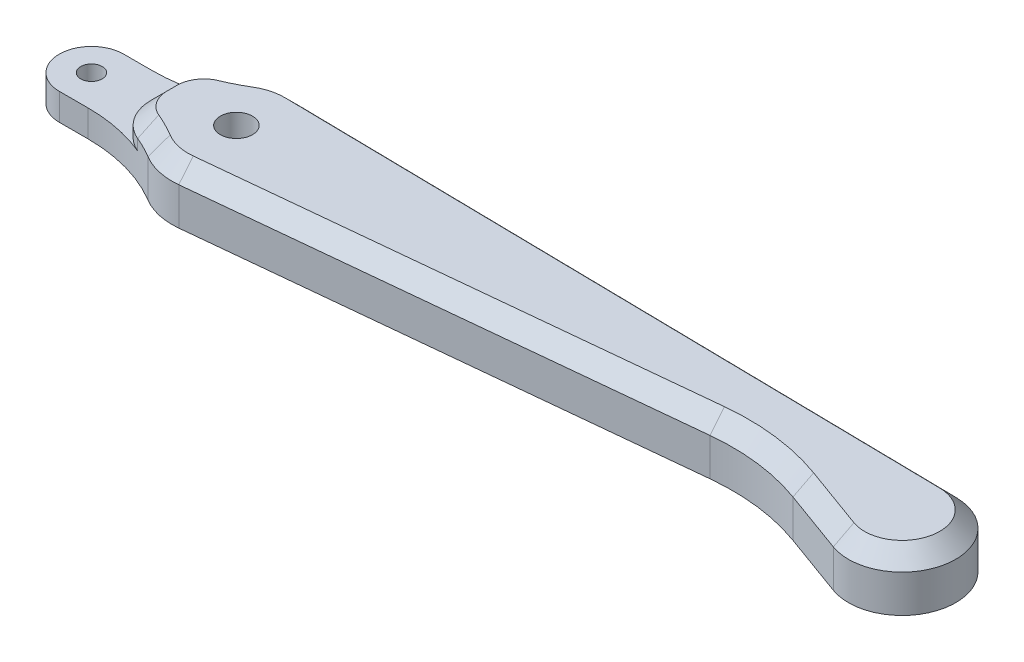
SolidWorks part; units mm, degrees
ref_plane "Front Plane" through (0, 0, 0) normal (0, 0, 1) x (1, 0, 0)
ref_plane "Top Plane" through (0, 0, 0) normal (0, 1, 0) x (1, 0, 0)
ref_plane "Right Plane" through (0, 0, 0) normal (1, 0, 0) x (0, 0, -1)
sketch "Sketch1" plane through (0, 0, 0) normal (0, 1, 0) x (1, 0, 0)
  line L0 (0, 0) -> (50, 0) construction
  line L1 (52, 0) -> (50, 0) construction
  line L2 (0.6, -5.9699) -> (50.1, -0.995)
  line L7 (0, 0) -> (-13.5, 0) construction
  line L10 (0.1053, 5.9991) -> (62.0806, 4.9993)
  line L11 (52, 0) -> (62, 0) construction
  line L12 (50.1, -0.995) -> (60.2921, -4.6993)
  line L16 (-13.5, 3) -> (-5.1962, 3)
  line L18 (-13.5, -3) -> (-5.1962, -3)
  arc A8 (60.2921, -4.6993) -> (62.0806, 4.9993) centre (62, 0) ccw
  circle A9 centre (50, 0) radius 1 construction
  arc A11 (-13.5, 3) -> (-13.5, -3) centre (-13.5, 0) ccw
  arc A12 (0.1053, 5.9991) -> (-5.1962, 3) centre (0, 0) ccw
  arc A13 (-5.1962, -3) -> (0.6, -5.9699) centre (0, 0) ccw
  circle A14 centre (0, 0) radius 1.5
  circle A15 centre (-13.5, 0) radius 1
  dimension "D1" = 12
  dimension "D3" = 3
  dimension "D6" = 10
  dimension "D8" = 2
  dimension "D4" = 6
  dimension "D5" = 2
  dimension "D9" = 6
  dimension "D2" = 62
  dimension "D7" = 13.5
extrude "Boss-Extrude1" add sketch "Sketch1" along normal blind 5
fillet "Fillet1" radius 20 1 edges at (50.1, 2.5, 0.995)
sketch "Sketch2" plane through (0, 5, 0) normal (0, 1, 0) x (1, 0, 0)
  line L0 (-13.5, 0) -> (-10.5, 0) construction
  line L1 (-10.5, 0) -> (-6.9257, 0) construction
  line L2 (-13.5, -3) -> (-5.1962, -3) construction
  line L3 (-13.5, 3) -> (-7.5, 3)
  line L5 (-13.5, -3) -> (-7.5, -3)
  line L6 (-7.5, 3) -> (-7.5, -3)
  arc A0 (-13.5, 3) -> (-13.5, -3) centre (-13.5, 0) ccw
  dimension "D1" = 6
extrude "Cut-Extrude1" cut sketch "Sketch2" against normal blind 2.5
fillet "Fillet5" radius 15 2 edges at (-5.1962, 2.5, 3) (-5.1962, 2.5, -3)
fillet "Fillet6" radius 4 2 edges at (-7.5, 3.75, -3.3713) (-7.5, 3.75, 3.3713)
chamfer "Chamfer1" distance 1.5 angle 45 12 edges at (-6.8288, 5, 2.6832) (-4.0474, 5, 4.6143) (-7.5, 5, 0) (-1.3121, 5, 5.8548) (-6.8288, 5, -2.6832) (23.0792, 5, 3.7107) (-4.0474, 5, -4.6143) (50.0363, 5, 1.5053) (-1.5528, 5, -5.7956) (57.341, 5, 3.6267) (31.093, 5, -5.4992) (66.9171, 5, 0.9068)
